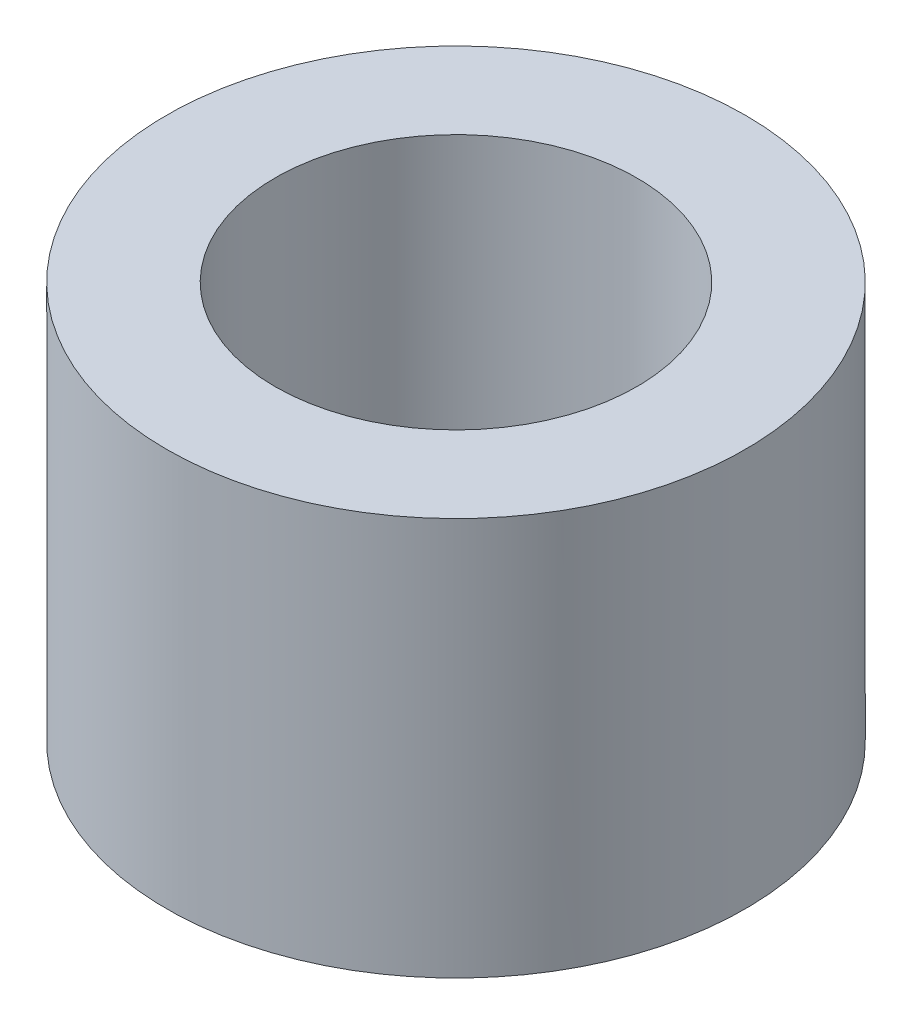
SolidWorks part; units mm, degrees
material "C (Graphite)"
ref_plane "Front Plane" through (0, 0, 0) normal (0, 0, 1) x (1, 0, 0)
ref_plane "Top Plane" through (0, 0, 0) normal (0, 1, 0) x (1, 0, 0)
ref_plane "Right Plane" through (0, 0, 0) normal (1, 0, 0) x (0, 0, -1)
sketch "Sketch1" plane through (0, 0, 0) normal (0, 1, 0) x (1, 0, 0)
  circle A0 centre (0, 0) radius 40
  circle A1 centre (0, 0) radius 25
  dimension "D1" = 80
  dimension "D2" = 50
extrude "Boss-Extrude1" add sketch "Sketch1" along normal blind 50
sketch "Sketch2" plane through (0, 0, 0) normal (0, -1, 0) x (1, 0, 0)
  circle A0 centre (0, 0) radius 37.5
  circle A1 centre (0, 0) radius 40
  dimension "D1" = 75
  dimension "D2" = 80
extrude "Boss-Extrude2" add sketch "Sketch2" along normal blind 5
